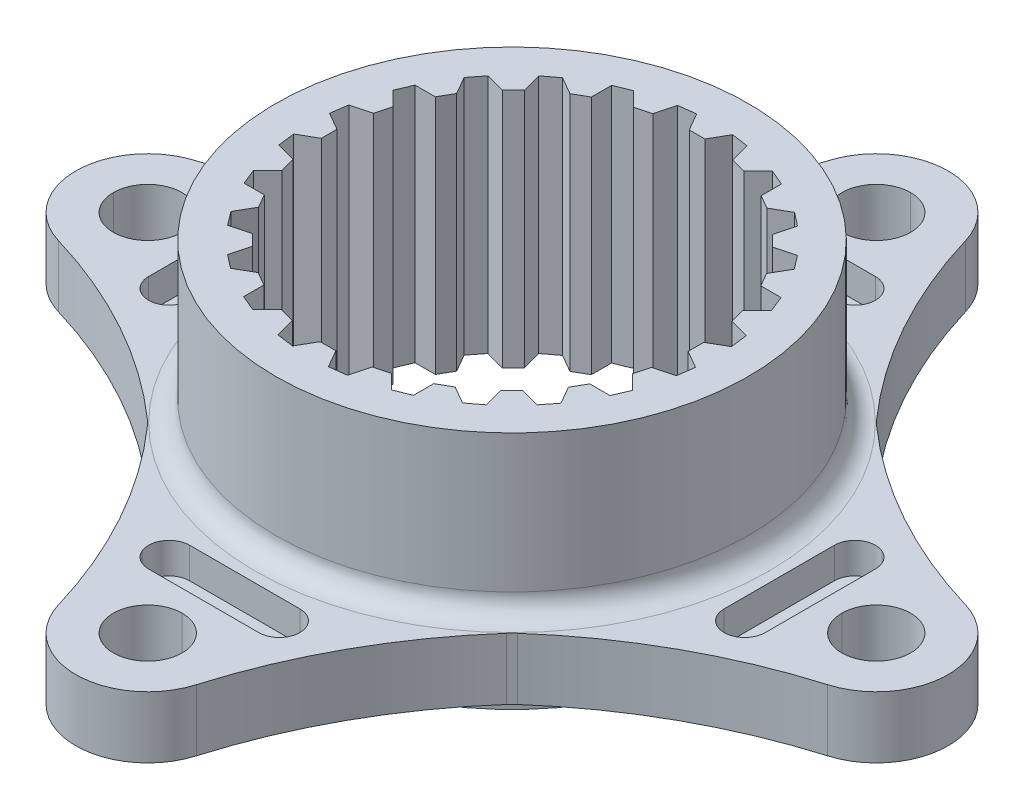
SolidWorks part; units mm, degrees
material "7075-T6 (SN)"
ref_plane "Front Plane" through (0, 0, 0) normal (0, 0, 1) x (1, 0, 0)
ref_plane "Top Plane" through (0, 0, 0) normal (0, 1, 0) x (1, 0, 0)
ref_plane "Right Plane" through (0, 0, 0) normal (1, 0, 0) x (0, 0, -1)
sketch "Sketch1" plane through (0, 0, 0) normal (0, 1, 0) x (1, 0, 0)
  line L0 (274.6284, 454.6081) -> (780.6456, 454.6081) construction
  circle A0 centre (0, 0) radius 23
  dimension "D1" = 46
sketch "Sketch5" plane through (0, 0, 0) normal (0, 1, 0) x (1, 0, 0)
  circle A0 centre (0, 0) radius 23
  circle A1 centre (0, 0) radius 25
  dimension "D1" = 46
  dimension "D2" = 50
sketch "Sketch6" plane through (0, 0, 0) normal (0, 1, 0) x (1, 0, 0)
  line L0 (-0.9689, -22.7363) -> (0.9689, -22.7363)
  line L1 (0.9689, -22.7363) -> (2.2189, -24.9013)
  line L2 (0, 33.3652) -> (0, -36.4848) construction
  line L3 (-0.9689, -22.7363) -> (-2.2189, -24.9013)
  line L4 (-4.9456, -22.1943) -> (-4.2985, -24.6091)
  line L5 (-6.8174, -21.6927) -> (-4.9456, -22.1943)
  line L6 (-6.8174, -21.6927) -> (-8.5852, -23.4605)
  line L7 (-10.5182, -22.6399) -> (-8.5852, -23.4605)
  line L8 (-10.5182, -20.1399) -> (-10.5182, -22.6399)
  line L9 (-12.1965, -19.171) -> (-10.5182, -20.1399)
  line L10 (-12.1965, -19.171) -> (-14.3615, -20.421)
  line L11 (-16.0164, -19.1281) -> (-14.3615, -20.421)
  line L12 (-15.3693, -16.7133) -> (-16.0164, -19.1281)
  line L13 (-16.7396, -15.343) -> (-15.3693, -16.7133)
  line L14 (-16.7396, -15.343) -> (-19.1544, -15.99)
  line L15 (-20.4182, -14.3129) -> (-19.1544, -15.99)
  line L16 (-19.1682, -12.1478) -> (-20.4182, -14.3129)
  line L17 (-20.1372, -10.4696) -> (-19.1682, -12.1478)
  line L18 (-20.1372, -10.4696) -> (-22.6372, -10.4696)
  line L19 (-23.4239, -8.5225) -> (-22.6372, -10.4696)
  line L20 (-21.6561, -6.7547) -> (-23.4239, -8.5225)
  line L21 (-22.1576, -4.8829) -> (-21.6561, -6.7547)
  line L22 (-22.1576, -4.8829) -> (-24.5725, -4.2358)
  line L23 (-24.8284, -2.1515) -> (-24.5725, -4.2358)
  line L24 (-22.6633, -0.9015) -> (-24.8284, -2.1515)
  line L25 (-22.6633, 1.0364) -> (-22.6633, -0.9015)
  line L26 (-22.6633, 1.0364) -> (-24.8284, 2.2864)
  line L27 (-24.5361, 4.366) -> (-24.8284, 2.2864)
  line L28 (-22.1213, 5.013) -> (-24.5361, 4.366)
  line L29 (-21.6197, 6.8849) -> (-22.1213, 5.013)
  line L30 (-21.6197, 6.8849) -> (-23.3875, 8.6526)
  line L31 (-22.567, 10.5857) -> (-23.3875, 8.6526)
  line L32 (-20.067, 10.5857) -> (-22.567, 10.5857)
  line L33 (-19.098, 12.2639) -> (-20.067, 10.5857)
  line L34 (-19.098, 12.2639) -> (-20.348, 14.429)
  line L35 (-19.0552, 16.0838) -> (-20.348, 14.429)
  line L36 (-16.6403, 15.4368) -> (-19.0552, 16.0838)
  line L37 (-15.27, 16.8071) -> (-16.6403, 15.4368)
  line L38 (-15.27, 16.8071) -> (-15.9171, 19.2219)
  line L39 (-14.24, 20.4857) -> (-15.9171, 19.2219)
  line L40 (-12.0749, 19.2357) -> (-14.24, 20.4857)
  line L41 (-10.3966, 20.2046) -> (-12.0749, 19.2357)
  line L42 (-10.3966, 20.2046) -> (-10.3966, 22.7046)
  line L43 (-8.4496, 23.4913) -> (-10.3966, 22.7046)
  line L44 (-6.6818, 21.7235) -> (-8.4496, 23.4913)
  line L45 (-4.8099, 22.2251) -> (-6.6818, 21.7235)
  line L46 (-4.8099, 22.2251) -> (-4.1629, 24.6399)
  line L47 (-2.0785, 24.8958) -> (-4.1629, 24.6399)
  line L48 (-0.8285, 22.7308) -> (-2.0785, 24.8958)
  line L49 (1.1093, 22.7308) -> (-0.8285, 22.7308)
  line L50 (1.1093, 22.7308) -> (2.3593, 24.8958)
  line L51 (4.4389, 24.6036) -> (2.3593, 24.8958)
  line L52 (5.086, 22.1888) -> (4.4389, 24.6036)
  line L53 (6.9578, 21.6872) -> (5.086, 22.1888)
  line L54 (6.9578, 21.6872) -> (8.7256, 23.455)
  line L55 (10.6586, 22.6344) -> (8.7256, 23.455)
  line L56 (10.6586, 20.1344) -> (10.6586, 22.6344)
  line L57 (12.3369, 19.1655) -> (10.6586, 20.1344)
  line L58 (12.3369, 19.1655) -> (14.5019, 20.4155)
  line L59 (16.1568, 19.1226) -> (14.5019, 20.4155)
  line L60 (15.5097, 16.7078) -> (16.1568, 19.1226)
  line L61 (16.88, 15.3375) -> (15.5097, 16.7078)
  line L62 (16.88, 15.3375) -> (19.2948, 15.9845)
  line L63 (20.5586, 14.3074) -> (19.2948, 15.9845)
  line L64 (19.3086, 12.1424) -> (20.5586, 14.3074)
  line L65 (20.2776, 10.4641) -> (19.3086, 12.1424)
  line L66 (20.2776, 10.4641) -> (22.7776, 10.4641)
  line L67 (23.5643, 8.517) -> (22.7776, 10.4641)
  line L68 (21.7965, 6.7492) -> (23.5643, 8.517)
  line L69 (22.298, 4.8774) -> (21.7965, 6.7492)
  line L70 (22.298, 4.8774) -> (24.7129, 4.2303)
  line L71 (24.9688, 2.146) -> (24.7129, 4.2303)
  line L72 (22.8037, 0.896) -> (24.9688, 2.146)
  line L73 (22.8037, -1.0419) -> (22.8037, 0.896)
  line L74 (22.8037, -1.0419) -> (24.9688, -2.2919)
  line L75 (24.6765, -4.3714) -> (24.9688, -2.2919)
  line L76 (22.2617, -5.0185) -> (24.6765, -4.3714)
  line L77 (21.7601, -6.8903) -> (22.2617, -5.0185)
  line L78 (21.7601, -6.8903) -> (23.5279, -8.6581)
  line L79 (22.7074, -10.5912) -> (23.5279, -8.6581)
  line L80 (20.2074, -10.5912) -> (22.7074, -10.5912)
  line L81 (19.2384, -12.2694) -> (20.2074, -10.5912)
  line L82 (19.2384, -12.2694) -> (20.4884, -14.4345)
  line L83 (19.1955, -16.0893) -> (20.4884, -14.4345)
  line L84 (16.7807, -15.4423) -> (19.1955, -16.0893)
  line L85 (15.4104, -16.8126) -> (16.7807, -15.4423)
  line L86 (15.4104, -16.8126) -> (16.0575, -19.2274)
  line L87 (14.3804, -20.4912) -> (16.0575, -19.2274)
  line L88 (12.2153, -19.2412) -> (14.3804, -20.4912)
  line L89 (10.537, -20.2101) -> (12.2153, -19.2412)
  line L90 (10.537, -20.2101) -> (10.537, -22.7101)
  line L91 (8.59, -23.4968) -> (10.537, -22.7101)
  line L92 (6.8222, -21.729) -> (8.59, -23.4968)
  line L93 (4.9503, -22.2306) -> (6.8222, -21.729)
  line L94 (4.9503, -22.2306) -> (4.3033, -24.6454)
  line L95 (2.2189, -24.9013) -> (4.3033, -24.6454)
  line L96 (-4.2985, -24.6091) -> (-2.2189, -24.9013)
  circle A0 centre (0, 0) radius 23 construction
  circle A1 centre (0, 0) radius 25 construction
  point P11 (0, -23)
  point P131 (0.0702, -0.0027)
  dimension "D4" = 2.5
  dimension "D1" = 2.1
  dimension "D5" = 112
  dimension "D6" = 120
  dimension "D2" = 1.9379
  dimension "D3" = 24
sketch "Sketch8" plane through (0, 0, 0) normal (0, 1, 0) x (1, 0, 0)
  circle A0 centre (0, 0) radius 100
  dimension "D1" = 200
extrude "Boss-Extrude4" add sketch "Sketch8" along normal blind 27.178 contours A0
extrude "Cut-Extrude1" cut sketch "Sketch6" along normal through all
sketch "Sketch9" plane through (0, 27.178, 0) normal (0, 1, 0) x (1, 0, 0)
  circle A0 centre (0, 0) radius 29.21
  dimension "D1" = 58.42
extrude "Cut-Extrude3" cut sketch "Sketch9" against normal blind 19.558 flip side to cut
sketch "Sketch10" plane through (0, 7.62, 0) normal (0, 1, 0) x (1, 0, 0)
  circle A1 centre (0, 45.0088) radius 4.2545
  circle A4 centre (45.0088, 0) radius 4.2545
  circle A5 centre (0, -45.0088) radius 4.2545
  circle A6 centre (-45.0088, 0) radius 4.2545
  point P11 (0, 0)
  point P28 (0, 0)
  dimension "D1" = 4
  dimension "D2" = 8.509
  dimension "D3" = 45.0088
sketch "Sketch11" plane through (0, 7.62, 0) normal (0, 1, 0) x (1, 0, 0)
  line L0 (0, 45.0088) -> (45.0088, 0) construction
  line L1 (0, 0) -> (70.7107, 70.7107) construction
  line L2 (0, 45.0088) -> (8.89, 45.0088) construction
  line L3 (0, 45.0088) -> (8.5239, 47.5337) construction
  circle A0 centre (0, 0) radius 100 construction
  arc A1 (8.5239, 47.5337) -> (22.5044, 22.5044) centre (71.1084, 66.0721) ccw
  arc A2 (47.5337, 8.5239) -> (22.5044, 22.5044) centre (66.0721, 71.1084) cw
  arc A3 (47.5337, -8.5239) -> (22.5044, -22.5044) centre (66.0721, -71.1084) ccw
  arc A4 (-8.5239, -47.5337) -> (-22.5044, -22.5044) centre (-71.1084, -66.0721) ccw
  arc A5 (-47.5337, 8.5239) -> (-22.5044, 22.5044) centre (-66.0721, 71.1084) ccw
  arc A6 (8.5239, -47.5337) -> (22.5044, -22.5044) centre (71.1084, -66.0721) cw
  arc A7 (-47.5337, -8.5239) -> (-22.5044, -22.5044) centre (-66.0721, -71.1084) cw
  circle A8 centre (0, 45.0088) radius 8.89
  circle A9 centre (45.0088, 0) radius 8.89
  circle A10 centre (0, -45.0088) radius 8.89
  circle A11 centre (-45.0088, 0) radius 8.89
  arc A12 (-8.5239, 47.5337) -> (-22.5044, 22.5044) centre (-71.1084, 66.0721) cw
  point P15 (0, 0)
  point P31 (0, 0)
  point P37 (0, 0)
  point P42 (0, 0)
  point P51 (0, 0)
  circle M10 centre (0, 0) radius 100
  dimension "D4" = 4
  dimension "D1" = 4
  dimension "D2" = 17.78
  dimension "D5" = 4
  dimension "D3" = 16.5
extrude "Cut-Extrude6" cut sketch "Sketch11" against normal blind 7.62 contours A11 A8 A9 A10 M10 region at (-97.1716, 7.62, 0)
extrude "Cut-Extrude7" cut sketch "Sketch10" against normal blind 7.62
fillet "Fillet2" radius 2.54 1 edges at (0, 7.62, 29.21)
ref_plane "Plane1" through (0, 0, 0) normal (0, 0, 1) x (1, 0, 0)
ref_plane "Plane2" through (0, 0, 0) normal (-1, 0, 0) x (0, 0, 1)
split line "Split Line1"
split line "Split Line2"
ref_axis "Axis1" through (0, 8.001, 0) along (0, -1, 0)
fillet "Fillet3" radius 7.62 4 edges at (-22.5044, 3.81, -22.5044) (22.5044, 3.81, -22.5044) (22.5044, 3.81, 22.5044) (-22.5044, 3.81, 22.5044)
sketch "Sketch13" plane through (0, 7.62, 0) normal (0, 1, 0) x (1, 0, 0)
  line L0 (0, 4.191) -> (0, -4.191) construction
  line L1 (-8.4262, 38.1) -> (8.4262, 38.1)
  line L2 (-8.4262, 38.1) -> (-10.795, 33.02)
  line L3 (-10.795, 33.02) -> (10.795, 33.02)
  line L4 (8.4262, 38.1) -> (10.795, 33.02)
  point P11 (0, 33.02)
  dimension "D1" = 115
  dimension "D2" = 115
  dimension "D3" = 5.08
  dimension "D4" = 0
  dimension "D5" = 21.59
  dimension "D6" = 33.02
extrude "Cut-Extrude12" cut sketch "Sketch13" against normal blind 3.81 contours L1 L4 L3 L2
fillet "Fillet5" radius 2.54 4 edges at (-10.795, 5.715, -33.02) (10.795, 5.715, -33.02) (-8.4262, 5.715, -38.1) (8.4262, 5.715, -38.1)
pattern_circular "CirPattern1" count 4 over 360 about axis through (0, 8.001, 0) along (0, -1, 0) of "Cut-Extrude12", "Fillet5"
sketch "Sketch14" plane through (0, 0, 0) normal (0, -1, 0) x (1, 0, 0)
  circle A0 centre (0, 0) radius 29.0322
  dimension "D1" = 58.0644
extrude "Boss-Extrude5" add sketch "Sketch14" along normal blind 2.54
extrude "Cut-Extrude17" cut sketch "Sketch6<5>" against normal blind 2.54
sketch "Sketch6<5>" plane through (0, 0, 0) normal (0, 1, 0) x (1, 0, 0) same geometry as "Sketch6"
